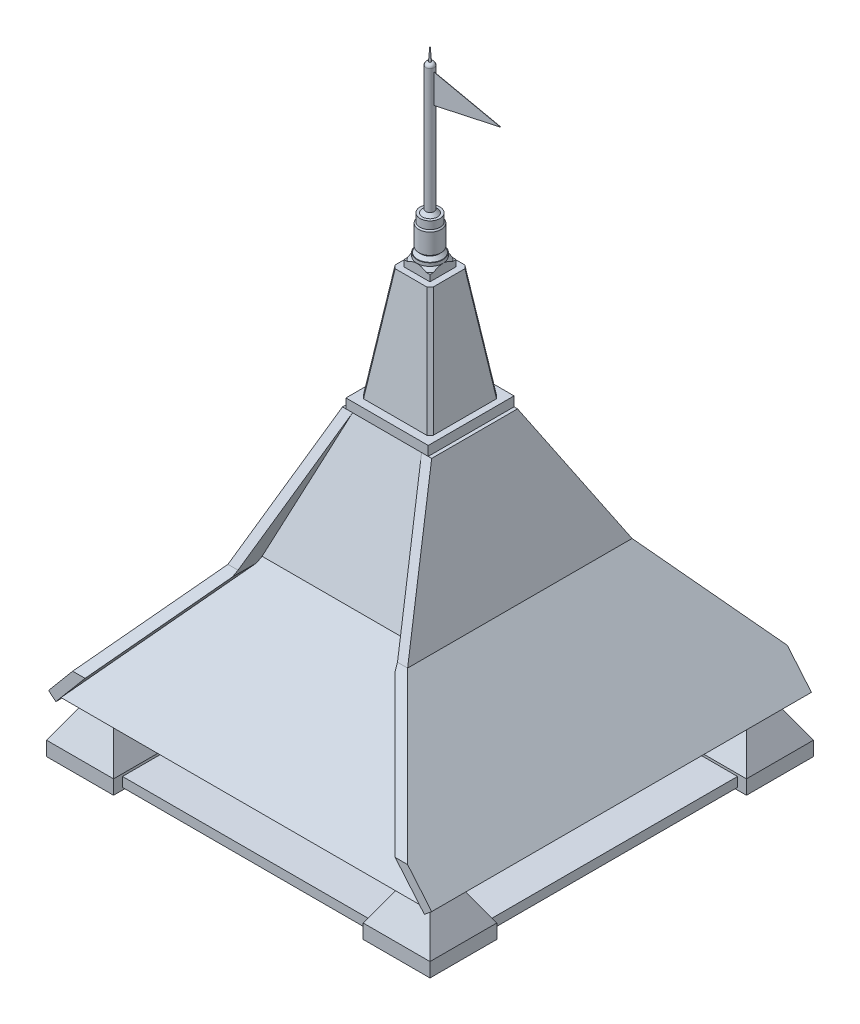
SolidWorks part; units mm, degrees
ref_plane "Front Plane" through (0, 0, 0) normal (0, 0, 1) x (1, 0, 0)
ref_plane "Top Plane" through (0, 0, 0) normal (0, 1, 0) x (1, 0, 0)
ref_plane "Right Plane" through (0, 0, 0) normal (1, 0, 0) x (0, 0, -1)
sketch "Sketch2" plane through (0, 0, 0) normal (0, 1, 0) x (1, 0, 0)
  line L0 (490, -425.6697) -> (490, -475)
  line L1 (490, -475) -> (510, -475)
  line L2 (-510, -425.6697) -> (-510, -475)
  line L3 (510, -425.6697) -> (510, -475)
  line L4 (574.3303, -510) -> (525, -510)
  line L5 (574.3303, -490) -> (525, -490)
  line L6 (525, -490) -> (525, -510)
  line L7 (490, -574.3303) -> (490, -525)
  line L8 (510, -574.3303) -> (510, -525)
  line L9 (510, -525) -> (490, -525)
  line L10 (425.6697, -490) -> (475, -490)
  line L11 (425.6697, -510) -> (475, -510)
  line L12 (475, -510) -> (475, -490)
  line L13 (500, -425) -> (500, -475) construction
  line L14 (490, 574.3303) -> (490, 525)
  line L15 (490, 525) -> (510, 525)
  line L16 (510, 574.3303) -> (510, 525)
  line L17 (574.3303, 490) -> (525, 490)
  line L18 (574.3303, 510) -> (525, 510)
  line L19 (525, 510) -> (525, 490)
  line L20 (490, 425.6697) -> (490, 475)
  line L21 (510, 425.6697) -> (510, 475)
  line L22 (510, 475) -> (490, 475)
  line L23 (425.6697, 510) -> (475, 510)
  line L24 (425.6697, 490) -> (475, 490)
  line L25 (475, 490) -> (475, 510)
  line L26 (500, 575) -> (500, 525) construction
  line L27 (-510, -475) -> (-490, -475)
  line L28 (-490, -425.6697) -> (-490, -475)
  line L29 (-425.6697, -510) -> (-475, -510)
  line L30 (-425.6697, -490) -> (-475, -490)
  line L31 (-475, -490) -> (-475, -510)
  line L32 (-510, -574.3303) -> (-510, -525)
  line L33 (-490, -574.3303) -> (-490, -525)
  line L34 (-490, -525) -> (-510, -525)
  line L35 (-574.3303, -490) -> (-525, -490)
  line L36 (-574.3303, -510) -> (-525, -510)
  line L37 (-525, -510) -> (-525, -490)
  line L38 (-510, 574.3303) -> (-510, 525)
  line L39 (-510, 525) -> (-490, 525)
  line L40 (-490, 574.3303) -> (-490, 525)
  line L41 (-425.6697, 490) -> (-475, 490)
  line L42 (-425.6697, 510) -> (-475, 510)
  line L43 (-475, 510) -> (-475, 490)
  line L44 (-510, 425.6697) -> (-510, 475)
  line L45 (-490, 425.6697) -> (-490, 475)
  line L46 (-490, 475) -> (-510, 475)
  line L47 (-574.3303, 510) -> (-525, 510)
  line L48 (-574.3303, 490) -> (-525, 490)
  line L49 (-525, 490) -> (-525, 510)
  line L50 (-500, -425) -> (-500, -475) construction
  line L51 (-500, 575) -> (-500, 525) construction
  line L52 (-605.7125, 605.7125) -> (-394.2875, 605.7125)
  line L53 (-605.7125, 605.7125) -> (-605.7125, 394.2875)
  line L54 (-605.7125, 394.2875) -> (-394.2875, 394.2875)
  line L55 (-394.2875, 605.7125) -> (-394.2875, 394.2875)
  line L56 (-605.7125, 605.7125) -> (-394.2875, 394.2875) construction
  line L57 (-605.7125, 394.2875) -> (-394.2875, 605.7125) construction
  line L58 (-605.7125, -394.2875) -> (-394.2875, -394.2875)
  line L59 (-605.7125, -394.2875) -> (-605.7125, -605.7125)
  line L60 (-605.7125, -605.7125) -> (-394.2875, -605.7125)
  line L61 (-394.2875, -394.2875) -> (-394.2875, -605.7125)
  line L62 (-605.7125, -394.2875) -> (-394.2875, -605.7125) construction
  line L63 (-605.7125, -605.7125) -> (-394.2875, -394.2875) construction
  line L64 (605.7125, 605.7125) -> (394.2875, 605.7125)
  line L65 (605.7125, 605.7125) -> (605.7125, 394.2875)
  line L66 (605.7125, 394.2875) -> (394.2875, 394.2875)
  line L67 (394.2875, 605.7125) -> (394.2875, 394.2875)
  line L68 (605.7125, 605.7125) -> (394.2875, 394.2875) construction
  line L69 (605.7125, 394.2875) -> (394.2875, 605.7125) construction
  line L70 (605.7125, -394.2875) -> (394.2875, -394.2875)
  line L71 (605.7125, -394.2875) -> (605.7125, -605.7125)
  line L72 (605.7125, -605.7125) -> (394.2875, -605.7125)
  line L73 (394.2875, -394.2875) -> (394.2875, -605.7125)
  line L74 (605.7125, -394.2875) -> (394.2875, -605.7125) construction
  line L75 (605.7125, -605.7125) -> (394.2875, -394.2875) construction
  arc A0 (490, -425.6697) -> (425.6697, -490) centre (500, -500) ccw
  arc A1 (425.6697, -510) -> (490, -574.3303) centre (500, -500) ccw
  arc A2 (510, -574.3303) -> (574.3303, -510) centre (500, -500) ccw
  arc A3 (574.3303, -490) -> (510, -425.6697) centre (500, -500) ccw
  arc A4 (490, -425.6697) -> (529.2889, -430.9554) centre (500, -500) cw
  arc A5 (490, 574.3303) -> (425.6697, 510) centre (500, 500) ccw
  arc A6 (425.6697, 490) -> (490, 425.6697) centre (500, 500) ccw
  arc A7 (510, 425.6697) -> (574.3303, 490) centre (500, 500) ccw
  arc A8 (574.3303, 510) -> (510, 574.3303) centre (500, 500) ccw
  arc A9 (490, 574.3303) -> (529.2889, 569.0446) centre (500, 500) cw
  arc A10 (-510, -425.6697) -> (-574.3303, -490) centre (-500, -500) ccw
  arc A11 (-574.3303, -510) -> (-510, -574.3303) centre (-500, -500) ccw
  arc A12 (-490, -574.3303) -> (-425.6697, -510) centre (-500, -500) ccw
  arc A13 (-425.6697, -490) -> (-490, -425.6697) centre (-500, -500) ccw
  arc A14 (-510, -425.6697) -> (-470.7111, -430.9554) centre (-500, -500) cw
  arc A15 (-510, 574.3303) -> (-574.3303, 510) centre (-500, 500) ccw
  arc A16 (-574.3303, 490) -> (-510, 425.6697) centre (-500, 500) ccw
  arc A17 (-490, 425.6697) -> (-425.6697, 490) centre (-500, 500) ccw
  arc A18 (-425.6697, 510) -> (-490, 574.3303) centre (-500, 500) ccw
  arc A19 (-510, 574.3303) -> (-470.7111, 569.0446) centre (-500, 500) cw
  circle A20 centre (0, 0) radius 157.4996
  point P22 (-500, -500)
  point P24 (-500, -500)
  point P48 (500, -500)
  point P49 (500, -500)
  point P71 (500, 500)
  point P72 (500, 500)
  point P87 (-500, 500)
  point P88 (-500, 500)
extrude "Boss-Extrude1" add sketch "Sketch2" along normal blind 60 contours L55 L52 L53 L54 A15 A19 A18 L42 L43 L41 A17 L45 L46 L44 A16 L48 L49 L47 | L64 L67 L66 L65 A5 A9 A8 L18 L19 L17 A7 L21 L22 L20 A6 L24 L25 L23 | L70 L73 L72 L71 A0 A4 A3 L5 L6 L4 A2 L8 L9 L7 A1 L11 L12 L10 | L61 L58 L59 L60 A10 A14 A13 L30 L31 L29 A12 L33 L34 L32 A11 L36 L37 L35 | A14 L2 L27 L28 | A4 L0 L1 L3 | A9 L14 L15 L16 | A19 L38 L39 L40
chamfer "Chamfer1" distance 15 angle 45 4 edges at (-500, 0, -605.7125) (-394.2875, 0, -500) (-500, 0, -394.2875) (-605.7125, 0, -500)
chamfer "Chamfer2" distance 15 angle 45 4 edges at (605.7125, 0, -500) (500, 0, -394.2875) (394.2875, 0, -500) (500, 0, -605.7125)
chamfer "Chamfer3" distance 15 angle 45 4 edges at (605.7125, 0, 500) (500, 0, 605.7125) (394.2875, 0, 500) (500, 0, 394.2875)
chamfer "Chamfer4" distance 15 angle 45 4 edges at (-605.7125, 0, 500) (-500, 0, 605.7125) (-394.2875, 0, 500) (-500, 0, 394.2875)
sketch "Sketch3" plane through (0, 0, 394.2875) normal (0, 0, -1) x (-1, 0, 0)
  line L0 (-500, 60) -> (-500, 15) construction
  line L1 (-605.7125, 60) -> (-394.2875, 60) construction
  line L2 (-605.7125, 15) -> (-394.2875, 15) construction
  line L4 (-577.5, 52.5) -> (-422.5, 52.5)
  line L5 (-577.5, 52.5) -> (-577.5, 22.5)
  line L6 (-577.5, 22.5) -> (-422.5, 22.5)
  line L7 (-422.5, 52.5) -> (-422.5, 22.5)
  line L8 (-577.5, 52.5) -> (-422.5, 22.5) construction
  line L9 (-577.5, 22.5) -> (-422.5, 52.5) construction
  point P6 (-500, 37.5)
extrude "Boss-Extrude2" add sketch "Sketch3" along normal up to surface (788.5751 mm away) up to face at (500, 37.5, -394.2875)
sketch "Sketch5" plane through (394.2875, 0, 0) normal (-1, 0, 0) x (0, 0, 1)
  line L0 (-500, 60) -> (-500, 15) construction
  line L1 (-605.7125, 60) -> (-394.2875, 60) construction
  line L2 (-605.7125, 15) -> (-394.2875, 15) construction
  line L4 (-577.5, 22.5) -> (-422.5, 22.5)
  line L5 (-577.5, 22.5) -> (-577.5, 52.5)
  line L6 (-577.5, 52.5) -> (-422.5, 52.5)
  line L7 (-422.5, 22.5) -> (-422.5, 52.5)
  line L8 (-577.5, 22.5) -> (-422.5, 52.5) construction
  line L9 (-577.5, 52.5) -> (-422.5, 22.5) construction
  point P6 (-500, 37.5)
extrude "Boss-Extrude3" add sketch "Sketch5" along normal up to next contours L4 L7 L6 L5
pattern_linear "LPattern1" count 2 spacing 1000 along (-1, 0, 0) of "Boss-Extrude2"
pattern_linear "LPattern2" count 2 spacing 1000 along (0, 0, 1) of "Boss-Extrude3"
sketch "Sketch6" plane through (0, 60, 0) normal (0, 1, 0) x (1, 0, 0)
  line L1 (-605.7125, 605.7125) -> (-394.2875, 605.7125)
  line L2 (-605.7125, 605.7125) -> (-605.7125, 394.2875)
  line L3 (-605.7125, 394.2875) -> (-394.2875, 394.2875)
  line L4 (-394.2875, 605.7125) -> (-394.2875, 394.2875)
  line L5 (-605.7125, 605.7125) -> (-394.2875, 394.2875) construction
  line L6 (-605.7125, 394.2875) -> (-394.2875, 605.7125) construction
  point P0 (-500, 500)
extrude "Boss-Extrude4" add sketch "Sketch6" along normal blind 95 draft 30
pattern_linear "LPattern3" count 2 spacing 1000 along (1, 0, 0) count 2 spacing 1000 along (0, 0, 1) of "Boss-Extrude4"
sketch "Sketch7" plane through (0, 0, 0) normal (0, 0, 1) x (1, 0, 0)
  line L0 (-130, 999.5654) -> (130, 999.5654)
  line L1 (130, 999.5654) -> (283.9091, 576.7037)
  line L2 (283.9091, 576.7037) -> (605.3029, 193.6815)
  line L3 (605.3029, 193.6815) -> (582.3215, 174.3978)
  line L4 (0, 1195.4824) -> (0, 821.9339) construction
  line L5 (183.9795, 851.2579) -> (155.7887, 840.9973) construction
  line L6 (43.2559, 999.5654) -> (43.2559, 969.5654) construction
  line L7 (-108.9938, 969.5654) -> (108.9938, 969.5654)
  line L8 (582.3215, 174.3978) -> (257.5275, 561.4723)
  line L9 (155.7887, 840.9973) -> (257.5275, 561.4723)
  line L10 (155.7887, 840.9973) -> (108.9938, 969.5654)
  line L11 (-43.2559, 999.5654) -> (-43.2559, 969.5654) construction
  line L12 (-183.9795, 851.2579) -> (-155.7887, 840.9973) construction
  line L13 (-155.7887, 840.9973) -> (-108.9938, 969.5654)
  line L14 (-155.7887, 840.9973) -> (-257.5275, 561.4723)
  line L15 (-582.3215, 174.3978) -> (-257.5275, 561.4723)
  line L16 (-605.3029, 193.6815) -> (-582.3215, 174.3978)
  line L17 (-283.9091, 576.7037) -> (-605.3029, 193.6815)
  line L18 (-130, 999.5654) -> (-283.9091, 576.7037)
  point P22 (0, 969.5654)
  point P25 (0, 999.5654)
  dimension "D1" = 160
extrude "Boss-Extrude5" add sketch "Sketch7" along normal mid plane 1200 separate body
sketch "Sketch9" plane through (0, 0, 0) normal (1, 0, 0) x (0, 0, -1)
  line L0 (-135.3029, 999.5654) -> (124.6971, 999.5654)
  line L1 (124.6971, 999.5654) -> (278.6062, 576.7037)
  line L2 (278.6062, 576.7037) -> (600, 193.6815)
  line L3 (600, 193.6815) -> (577.0187, 174.3978)
  line L4 (178.6766, 851.2579) -> (150.4859, 840.9973) construction
  line L5 (37.9531, 999.5654) -> (37.9531, 969.5654) construction
  line L6 (-114.2966, 969.5654) -> (103.6909, 969.5654)
  line L7 (577.0187, 174.3978) -> (252.2246, 561.4723)
  line L8 (150.4859, 840.9973) -> (252.2246, 561.4723)
  line L9 (150.4859, 840.9973) -> (103.6909, 969.5654)
  line L10 (-48.5588, 999.5654) -> (-48.5588, 969.5654) construction
  line L11 (-189.2824, 851.2579) -> (-161.0916, 840.9973) construction
  line L12 (-161.0916, 840.9973) -> (-114.2966, 969.5654)
  line L13 (-161.0916, 840.9973) -> (-262.8304, 561.4723)
  line L14 (-587.6244, 174.3978) -> (-262.8304, 561.4723)
  line L15 (-610.6057, 193.6815) -> (-587.6244, 174.3978)
  line L16 (-289.2119, 576.7037) -> (-610.6057, 193.6815)
  line L17 (-135.3029, 999.5654) -> (-289.2119, 576.7037)
  point P18 (-5.3029, 969.5654)
  point P21 (-5.3029, 999.5654)
  dimension "D1" = 160
extrude "Boss-Extrude6" add sketch "Sketch9" along normal up to next and the other way up to next contours L0 L17 L16 L15 L14 L13 L12 L6 L9 L8 L7 L3 L2 L1
ref_plane "Plane1" through (0, 0, 0) normal (0, 0, 1) x (1, 0, 0)
mirror "Mirror1" about plane through (0, 0, 0) normal (0, 0, 1) of "Boss-Extrude6"
sketch "Sketch10" plane through (0, 0, 0) normal (1, 0, 0) x (0, 0, -1)
  line L0 (-600, 284.342) -> (-354.6794, 576.7037)
  line L1 (-600, 193.6815) -> (-600, 576.7037) construction
  line L2 (-600, 576.7037) -> (600, 576.7037) construction
  line L3 (-354.6794, 576.7037) -> (-135.6162, 969.5654)
  line L4 (-135.6162, 969.5654) -> (-135.6162, 999.5654)
  line L5 (-600, 999.5654) -> (600, 999.5654) construction
  line L6 (-135.6162, 999.5654) -> (-600, 999.5654)
  line L7 (135.6162, 999.5654) -> (135.6162, 969.5654)
  line L8 (135.6162, 969.5654) -> (354.6794, 576.7037)
  line L9 (354.6794, 576.7037) -> (600, 284.342)
  line L10 (600, 193.6815) -> (600, 576.7037) construction
  line L11 (600, 284.342) -> (600, 999.5654)
  line L12 (600, 999.5654) -> (135.6162, 999.5654)
  line L13 (-600, 999.5654) -> (-600, 284.342)
  line L14 (-291.3869, 561.4723) -> (-600, 193.6815) construction
  line L15 (291.3869, 561.4723) -> (600, 193.6815) construction
extrude "Cut-Extrude1" cut sketch "Sketch10" against normal mid plane 1200
sketch "Sketch11" plane through (0, 0, -135.6162) normal (0, 0, -1) x (-1, 0, 0)
  line L1 (130, 999.5654) -> (140.9191, 999.5654)
  line L2 (130, 999.5654) -> (130, 969.5654)
  line L3 (130, 969.5654) -> (140.9191, 969.5654)
  line L4 (140.9191, 999.5654) -> (140.9191, 969.5654)
  line L5 (-130, 999.5654) -> (-140.9191, 999.5654)
  line L6 (-130, 999.5654) -> (-130, 969.5654)
  line L7 (-130, 969.5654) -> (-140.9191, 969.5654)
  line L8 (-140.9191, 999.5654) -> (-140.9191, 969.5654)
extrude "Cut-Extrude2" cut sketch "Sketch11" against normal blind 1200
sketch "Sketch13" plane through (0, 999.5654, 0) normal (0, 1, 0) x (1, 0, 0)
  line L1 (-110.2083, 110.2083) -> (110.2083, 110.2083)
  line L2 (-110.2083, 110.2083) -> (-110.2083, -110.2083)
  line L3 (-110.2083, -110.2083) -> (110.2083, -110.2083)
  line L4 (110.2083, 110.2083) -> (110.2083, -110.2083)
  line L5 (-110.2083, 110.2083) -> (110.2083, -110.2083) construction
  line L6 (-110.2083, -110.2083) -> (110.2083, 110.2083) construction
  point P0 (0, 0)
extrude "Boss-Extrude7" add sketch "Sketch13" along normal blind 356 draft 8
chamfer "Chamfer5" distance 10 angle 45 4 edges at (-85.192, 1177.5654, -85.192) (85.192, 1177.5654, -85.192) (85.192, 1177.5654, 85.192) (-85.192, 1177.5654, 85.192)
sketch "Sketch14" plane through (0, 1355.5654, 0) normal (0, 1, 0) x (1, 0, 0)
  line L1 (-41.069, 41.2432) -> (41.069, 41.2432)
  line L2 (-41.069, 41.2432) -> (-41.069, -41.2432)
  line L3 (-41.069, -41.2432) -> (41.069, -41.2432)
  line L4 (41.069, 41.2432) -> (41.069, -41.2432)
  line L5 (-41.069, 41.2432) -> (41.069, -41.2432) construction
  line L6 (-41.069, -41.2432) -> (41.069, 41.2432) construction
  point P0 (0, 0)
extrude "Boss-Extrude8" add sketch "Sketch14" along normal blind 20
sketch "Sketch15" plane through (0, 1375.5654, 0) normal (0, 1, 0) x (1, 0, 0)
  circle A0 centre (0, 0) radius 41.069
extrude "Boss-Extrude9" add sketch "Sketch15" along normal blind 20
sketch "Sketch16" plane through (0, 1395.5654, 0) normal (0, 1, 0) x (1, 0, 0)
  circle A0 centre (0, 0) radius 29.1277
extrude "Boss-Extrude10" add sketch "Sketch16" along normal blind 20
sketch "Sketch17" plane through (0, 1415.5654, 0) normal (0, 1, 0) x (1, 0, 0)
  circle A0 centre (0, 0) radius 35.4031
extrude "Boss-Extrude11" add sketch "Sketch17" along normal blind 70
sketch "Sketch18" plane through (0, 1485.5654, 0) normal (0, 1, 0) x (1, 0, 0)
  circle A0 centre (0, 0) radius 31.5552
extrude "Boss-Extrude12" add sketch "Sketch18" along normal blind 18
sketch "Sketch19" plane through (0, 1503.5654, 0) normal (0, 1, 0) x (1, 0, 0)
  circle A0 centre (0, 0) radius 13.3588
extrude "Boss-Extrude13" add sketch "Sketch19" along normal blind 414
fillet "Fillet1" radius 10 1 edges at (0, 1917.5654, 13.3588)
chamfer "Chamfer6" distance 10 angle 45 8 edges at (0, 1375.5654, 41.069) (0, 1375.5654, -41.069) (0, 1395.5654, 29.1277) (0, 1415.5654, 29.1277) (0, 1415.5654, 35.4031) (0, 1485.5654, 35.4031) (0, 1485.5654, 31.5552) (0, 1503.5654, 13.3588)
sketch "Sketch20" plane through (0, 1917.5654, 0) normal (0, 1, 0) x (1, 0, 0)
  circle A0 centre (0, 0) radius 3.3588
extrude "Boss-Extrude14" add sketch "Sketch20" along normal blind 42 draft 4
sketch "Sketch21" plane through (0, 0, 0) normal (0, 0, 1) x (1, 0, 0)
  line L0 (13.3588, 1895.145) -> (223.6092, 1849.6152)
  line L1 (13.3588, 1513.5654) -> (13.3588, 1907.5654) construction
  line L2 (223.6092, 1849.6152) -> (13.3588, 1804.0855)
  line L3 (13.3588, 1804.0855) -> (13.3588, 1895.145)
extrude "Boss-Extrude15" add sketch "Sketch21" along normal mid plane 1 separate body
sketch "Sketch23" plane through (0, 155, 0) normal (0, 1, 0) x (1, 0, 0)
  line L0 (-550.8642, 500) -> (-449.1358, 500) construction
  line L1 (-550.8642, 550.8642) -> (-550.8642, 449.1358) construction
  line L2 (-449.1358, 449.1358) -> (-449.1358, 550.8642) construction
  line L4 (449.1358, 550.8642) -> (449.1358, 449.1358) construction
  line L5 (449.1358, 500) -> (550.8642, 500) construction
  line L6 (550.8642, 449.1358) -> (550.8642, 550.8642) construction
  line L7 (550.8642, -500) -> (449.1358, -500) construction
  line L8 (550.8642, -550.8642) -> (550.8642, -449.1358) construction
  line L9 (449.1358, -449.1358) -> (449.1358, -550.8642) construction
  line L10 (-532.108, 532.108) -> (-467.892, 532.108)
  line L11 (-449.1358, -550.8642) -> (-449.1358, -449.1358) construction
  line L12 (-449.1358, -500) -> (-550.8642, -500) construction
  line L13 (-550.8642, -449.1358) -> (-550.8642, -550.8642) construction
  line L14 (-532.108, 532.108) -> (-532.108, 467.892)
  line L15 (-532.108, 467.892) -> (-467.892, 467.892)
  line L16 (-467.892, 532.108) -> (-467.892, 467.892)
  line L17 (-532.108, 532.108) -> (-467.892, 467.892) construction
  line L18 (-532.108, 467.892) -> (-467.892, 532.108) construction
  line L19 (467.892, 532.108) -> (532.108, 532.108)
  line L20 (467.892, 532.108) -> (467.892, 467.892)
  line L21 (467.892, 467.892) -> (532.108, 467.892)
  line L22 (532.108, 532.108) -> (532.108, 467.892)
  line L23 (467.892, 532.108) -> (532.108, 467.892) construction
  line L24 (467.892, 467.892) -> (532.108, 532.108) construction
  line L25 (467.892, -467.892) -> (532.108, -467.892)
  line L26 (467.892, -467.892) -> (467.892, -532.108)
  line L27 (467.892, -532.108) -> (532.108, -532.108)
  line L28 (532.108, -467.892) -> (532.108, -532.108)
  line L29 (467.892, -467.892) -> (532.108, -532.108) construction
  line L30 (467.892, -532.108) -> (532.108, -467.892) construction
  line L31 (-467.892, -467.892) -> (-532.108, -467.892)
  line L32 (-467.892, -467.892) -> (-467.892, -532.108)
  line L33 (-467.892, -532.108) -> (-532.108, -532.108)
  line L34 (-532.108, -467.892) -> (-532.108, -532.108)
  line L35 (-467.892, -467.892) -> (-532.108, -532.108) construction
  line L36 (-467.892, -532.108) -> (-532.108, -467.892) construction
  point P18 (-500, 500)
  point P29 (500, 500)
  point P34 (500, -500)
  point P39 (-500, -500)
extrude "Boss-Extrude16" add sketch "Sketch23" along normal up to next
